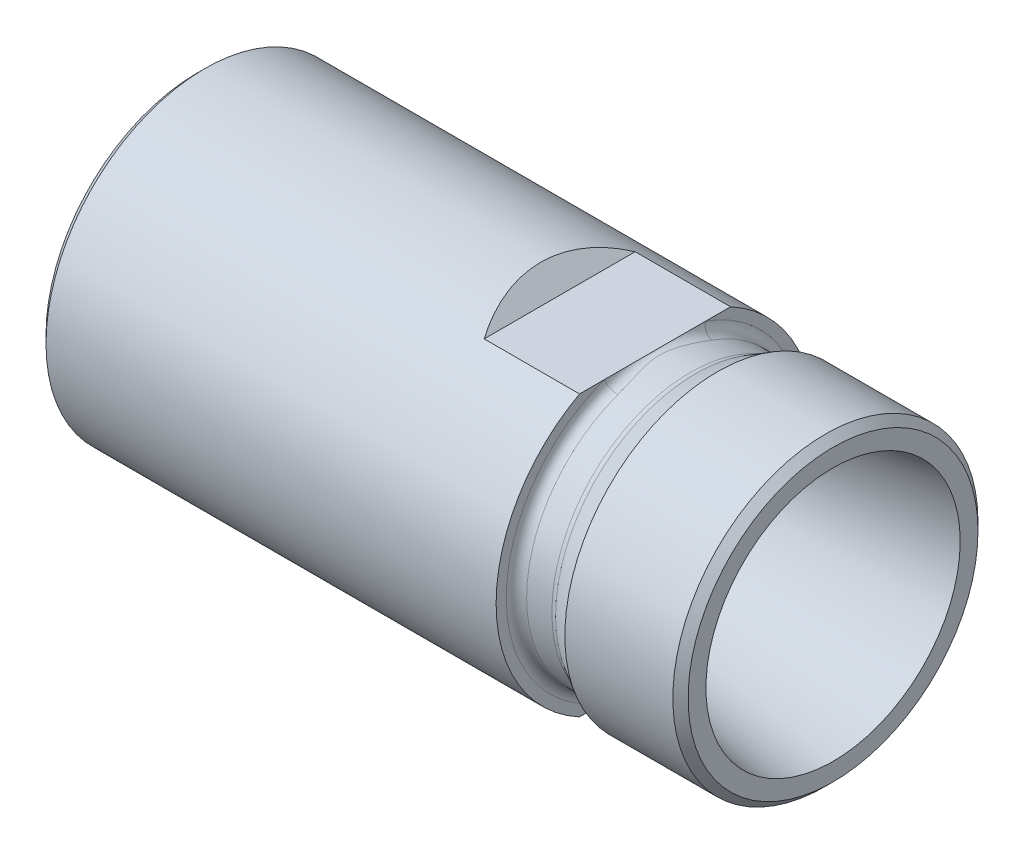
SolidWorks part; units mm, degrees
material "1.1193 (C45G)"
ref_plane "Přední rovina" through (0, 0, 0) normal (0, 0, 1) x (1, 0, 0)
ref_plane "Horní rovina" through (0, 0, 0) normal (0, 1, 0) x (1, 0, 0)
ref_plane "Pravá rovina" through (0, 0, 0) normal (1, 0, 0) x (0, 0, -1)
sketch "Skica1" plane through (0, 0, 0) normal (0, 0, 1) x (1, 0, 0)
  line L0 (0, 12.5) -> (0, 0)
  line L1 (0, 0) -> (36, 0)
  line L2 (36, 0) -> (36, 12.5)
  line L3 (36, 12.5) -> (0, 12.5)
  line L4 (0, 0) -> (36, 0) construction
revolve "Rotovat1" add sketch "Skica1" angle 360 about L4
sketch "Skica2" plane through (36, 0, 0) normal (1, 0, 0) x (0, 0, -1)
  line L0 (5.9372, -11) -> (-5.9372, -11)
  arc A0 (-5.9372, -11) -> (5.9372, -11) centre (0, 0) ccw
extrude "Odebrat vysunutím1" cut sketch "Skica2" against normal blind 7.5
sketch "Skica3" plane through (36, 0, 0) normal (1, 0, 0) x (0, 0, -1)
  line L0 (-5.9372, 11) -> (5.9372, 11)
  arc A0 (5.9372, 11) -> (-5.9372, 11) centre (0, 0) ccw
extrude "Odebrat vysunutím2" cut sketch "Skica3" against normal blind 7.5
sketch "Skica4" plane through (36, 0, 0) normal (1, 0, 0) x (0, 0, -1)
  circle A0 centre (0, 0) radius 10.9
extrude "Přidat vysunutím1" add sketch "Skica4" along normal blind 3
sketch "Skica5" plane through (39, 0, 0) normal (1, 0, 0) x (0, 0, -1)
  circle A0 centre (0, 0) radius 10.9
extrude "Přidat vysunutím2" add sketch "Skica5" along normal blind 1.9053 draft 30 draft outward yes
sketch "Skica6" plane through (40.9053, 0, 0) normal (1, 0, 0) x (0, 0, -1)
  circle A0 centre (0, 0) radius 12
extrude "Přidat vysunutím3" add sketch "Skica6" along normal blind 9.0947
draft "Úkos1" type of draft neutral plane draft angle 45 faces to draft 1 face at (28.5, 11.75, 0) neutral plane through (28.5, 11, 5.9372) neutral plane normal (0, 1, 0) parameters "D1"=45
draft "Úkos2" type of draft neutral plane draft angle 45 faces to draft 1 face at (28.5, -11.75, 0) neutral plane through (28.5, -11, -5.9372) neutral plane normal (0, -1, 0) parameters "D1"=45
hole_wizard "Válcové zahloubení pro M8 šrouby se šestihrannou hlavou1" positions "Skica8" profile "Skica7" counterbore size "M8" standard "ANSI Metric"
sketch "Skica8" plane through (50, 0, 0) normal (1, 0, 0) x (0, 0, -1)
  point P0 (0, 0)
sketch "Skica7" plane through (50, 0, 0) normal (0, 1, 0) x (0, 0, -1)
  line L0 (0, 0) -> (0, 50)
  line L1 (0, 50) -> (4.2164, 50)
  line L3 (4.2164, 50) -> (4.2164, 36)
  line L4 (4.2164, 36) -> (7.7, 36)
  line L5 (7.7, 36) -> (7.7, 0)
  line L7 (7.7, 0) -> (0, 0)
  line L11 (0, -6.35) -> (0, 107.95) construction
  dimension "Průměr díry skrz" = 8.4328
  dimension "Hloubka díry skrz" = 50
  dimension "Průměr válcového zahloubení" = 15.4
  dimension "Hloubka válcového zahloubení" = 36
chamfer "Zkosení1" distance 0.5832 angle 60 1 edges at (0, 0, -4.2164)
chamfer "Zkosení2" distance 0.6 angle 45 2 edges at (0, 0, -12.5) (50, 0, -12)
chamfer "Zkosení3" distance 2.3 angle 82 1 edges at (50, 0, -7.7)
fillet "Zaoblit1" radius 0.8 2 edges at (39, 0, -10.9) (36, 0, -10.9)
